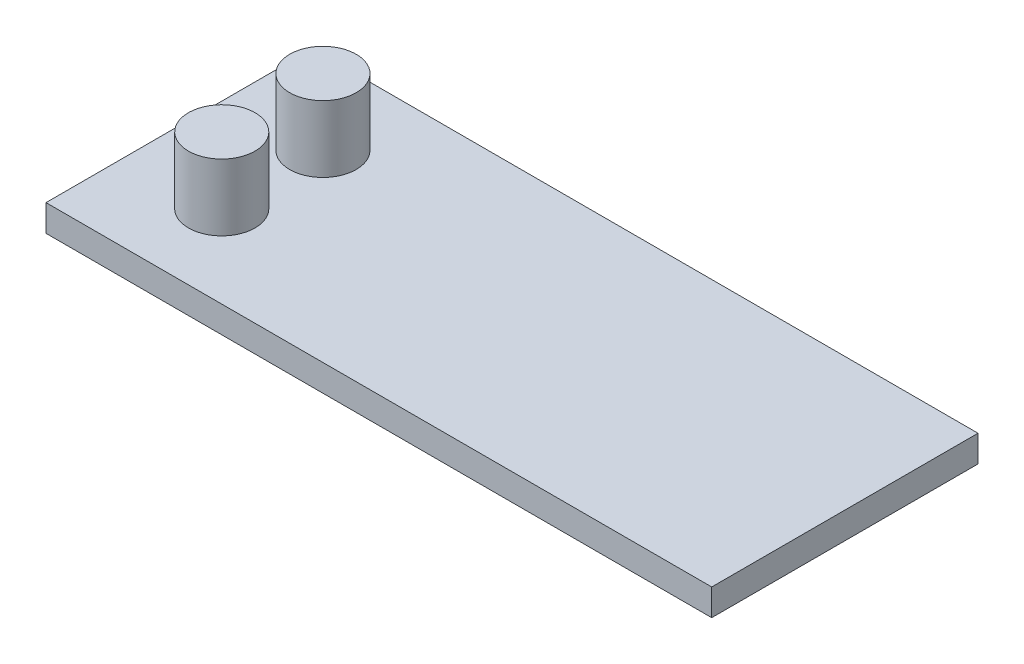
SolidWorks part; units mm, degrees
material "ABS"
ref_plane "前视基准面" through (0, 0, 0) normal (0, 0, 1) x (1, 0, 0)
ref_plane "上视基准面" through (0, 0, 0) normal (0, 1, 0) x (1, 0, 0)
ref_plane "右视基准面" through (0, 0, 0) normal (1, 0, 0) x (0, 0, -1)
sketch "草图1" plane through (0, 0, 0) normal (0, 1, 0) x (1, 0, 0)
  line L0 (-27.5, 0) -> (27.5, 0) construction
  line L1 (-25, -10) -> (25, -10)
  line L2 (-25, -10) -> (-25, 10)
  line L3 (-25, 10) -> (25, 10)
  line L4 (25, -10) -> (25, 10)
  line L5 (-25, -10) -> (25, 10) construction
  line L6 (-25, 10) -> (25, -10) construction
  circle A0 centre (-18, 3.8) radius 2.5
  circle A1 centre (-18, -3.8) radius 2.5
  point P0 (0, 0)
  dimension "D3" = 5
  dimension "D1" = 50
  dimension "D2" = 20
  dimension "D4" = 3.8
  dimension "D5" = 18
extrude "凸台-拉伸1" add sketch "草图1" along normal blind 2 contours A0 | A1 | L2 L1 L4 L3
extrude "凸台-拉伸2" add sketch "草图1<3>" along normal blind 7 contours A0 | A1 region at (-18, 0, -3.8) region at (-18, 0, 3.8)
sketch "草图1<3>" plane through (0, 0, 0) normal (0, 1, 0) x (1, 0, 0) same geometry as "草图1"
